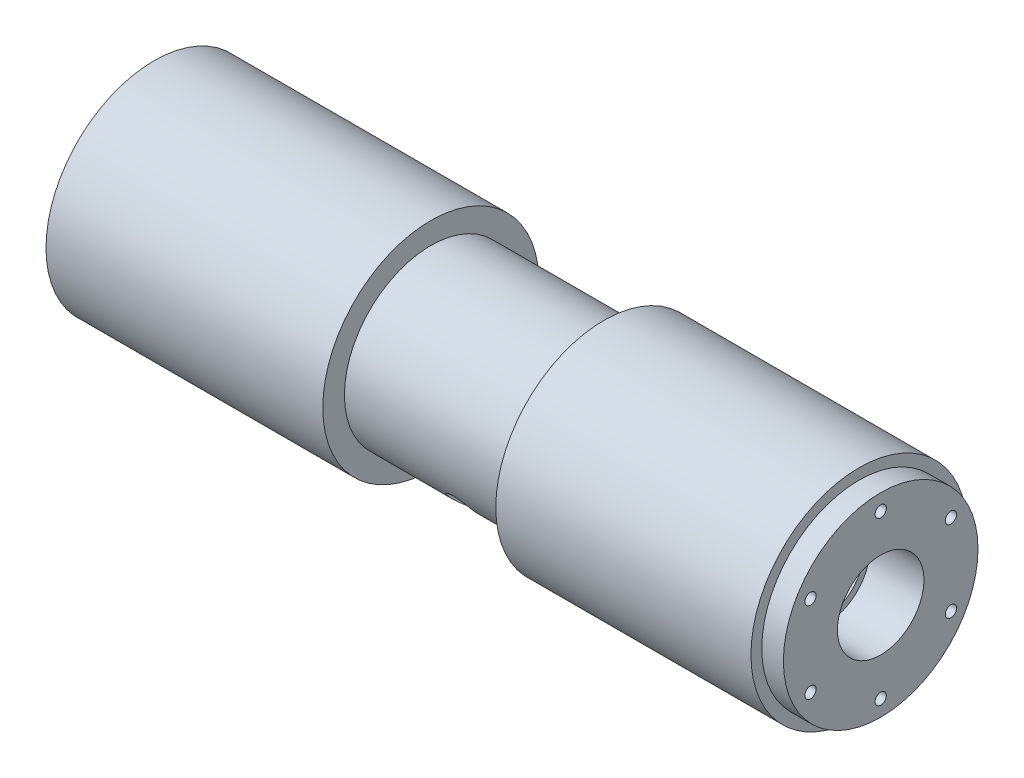
SolidWorks part; units mm, degrees
material "Nylon 101"
ref_plane "Front Plane" through (0, 0, 0) normal (0, 0, 1) x (1, 0, 0)
ref_plane "Top Plane" through (0, 0, 0) normal (0, 1, 0) x (1, 0, 0)
ref_plane "Right Plane" through (0, 0, 0) normal (1, 0, 0) x (0, 0, -1)
sketch "Sketch1" plane through (0, 0, 0) normal (1, 0, 0) x (0, 0, -1)
  circle A0 centre (0, 0) radius 31.75
  circle A1 centre (0, 0) radius 10.795
  dimension "D2" = 63.5
  dimension "D1" = 20.955
extrude "Boss-Extrude1" add sketch "Sketch1" along normal blind 106.68
sketch "Sketch2" plane through (0, 0, 0) normal (-1, 0, 0) x (0, 0, 1)
  circle A0 centre (0, 0) radius 12.7
extrude "Cut-Extrude1" cut sketch "Sketch2" against normal blind 15.875
mirror "Mirror1" about plane through (106.68, 0, 0) normal (1, 0, 0) of "Cut-Extrude1", "Boss-Extrude1"
sketch "Sketch3" plane through (0, 0, 0) normal (-1, 0, 0) x (0, 0, 1)
  circle A0 centre (0, 0) radius 25.4
  dimension "D1" = 50.8
extrude "Cut-Extrude2" cut sketch "Sketch3" against normal blind 50.8 from offset 81.28 flip side to cut offset against normal yes
sketch "Sketch5" plane through (0, 0, 0) normal (0, 0, 1) x (1, 0, 0)
  line L0 (213.36, -31.75) -> (213.36, 31.75) construction
  line L1 (132.08, 25.4) -> (81.28, 25.4) construction
  circle A0 centre (109.22, -17.4625) radius 3.9687
  dimension "D1" = 7.9375
  dimension "D3" = 42.8625
  dimension "D2" = 104.14
extrude "Cut-Extrude3" cut sketch "Sketch5" against normal blind 25.4 and the other way blind 25.4
hole_wizard "M4x0.7 Tapped Hole1" positions "Sketch10" profile "Sketch9" tap size "M4x0.7" standard "ANSI Metric"
sketch "Sketch10" plane through (213.36, 0, 0) normal (1, 0, 0) x (0, 0, -1)
  line L1 (20.6222, -11.9062) -> (20.6222, 11.9062)
  line L2 (20.6222, 11.9062) -> (0, 23.8125)
  line L3 (0, 23.8125) -> (-20.6222, 11.9062)
  line L4 (-20.6222, 11.9062) -> (-20.6222, -11.9062)
  line L5 (-20.6222, -11.9062) -> (0, -23.8125)
  line L6 (0, -23.8125) -> (20.6222, -11.9062)
  circle A0 centre (0, 0) radius 23.8125
  circle A1 centre (0, 0) radius 20.6222 construction
  point P0 (20.6222, -11.9062)
  point P2 (0, -23.8125)
  point P4 (20.6222, 11.9062)
  point P6 (0, 23.8125)
  point P8 (-20.6222, 11.9062)
  point P10 (-20.6222, -11.9062)
  dimension "D1" = 47.625
sketch "Sketch9" plane through (213.36, -11.9062, -20.6222) normal (0, 1, 0) x (0, 0, -1)
  line L0 (0, 0) -> (0, 10.8974)
  line L1 (0, 10.8974) -> (1.65, 9.906)
  line L2 (1.65, 9.906) -> (1.65, 0)
  line L5 (1.65, 0) -> (0, 0)
  line L10 (0, 10.8974) -> (-1.65, 9.906) construction
  line L11 (0, -6.35) -> (0, 107.95) construction
  dimension "Tap Drill Dia." = 3.3
  dimension "Tap Drill Depth" = 9.906
  dimension "Drill Angle" = 118
sketch "Sketch11" plane through (213.36, 0, 0) normal (1, 0, 0) x (0, 0, -1)
  circle A0 centre (0, 0) radius 28.575
  dimension "D1" = 57.15
extrude "Cut-Extrude4" cut sketch "Sketch11" against normal blind 6.35 flip side to cut
